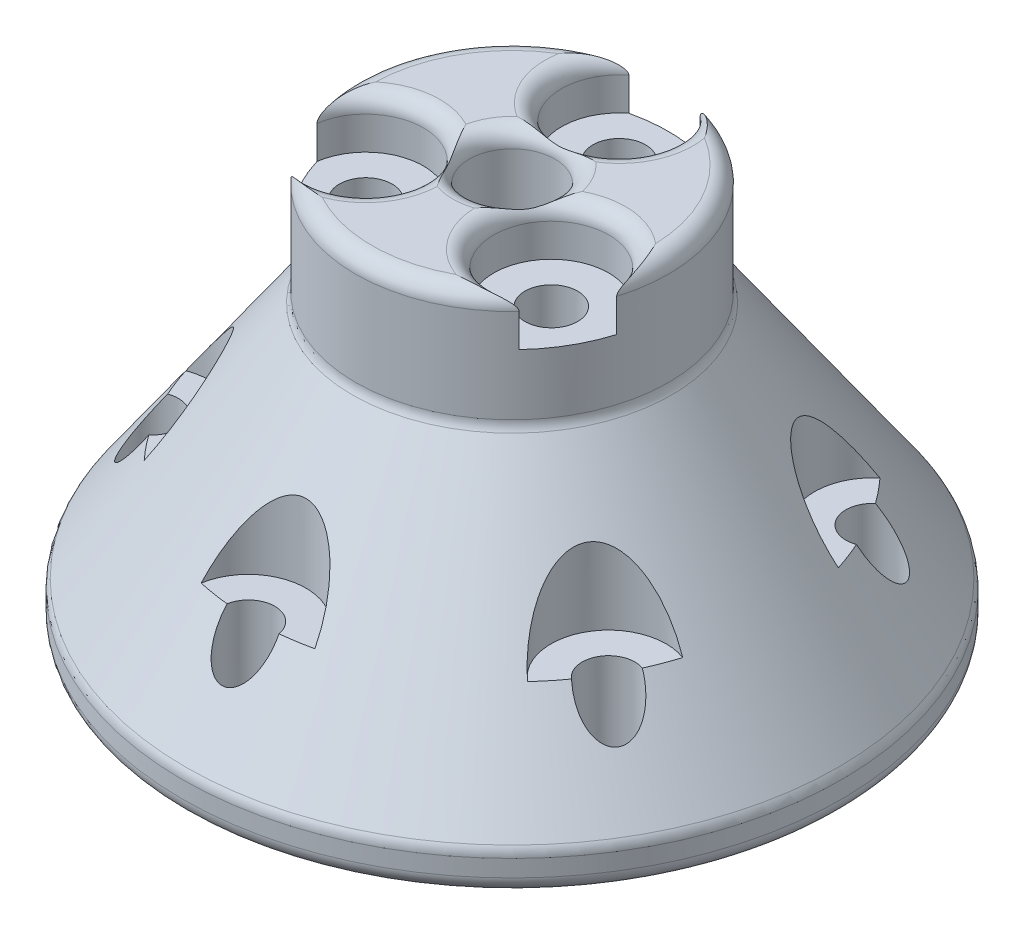
SolidWorks part; units mm, degrees
ref_plane "Front Plane" through (0, 0, 0) normal (0, 0, 1) x (1, 0, 0)
ref_plane "Top Plane" through (0, 0, 0) normal (0, 1, 0) x (1, 0, 0)
ref_plane "Right Plane" through (0, 0, 0) normal (1, 0, 0) x (0, 0, -1)
sketch "Sketch1" plane through (0, 0, 0) normal (0, 1, 0) x (1, 0, 0)
  circle A0 centre (0, 0) radius 20
  circle A1 centre (0, 0) radius 2.6
  dimension "D1" = 5.2
  dimension "D2" = 40
extrude "Boss-Extrude1" add sketch "Sketch1" along normal up to surface (24.34 mm away)
sketch "Sketch6" plane through (0, 24.34, 0) normal (0, 1, 0) x (1, 0, 0)
  circle A0 centre (0, 0) radius 9.5
  circle A1 centre (0, 0) radius 20 construction
  circle A2 centre (0, 0) radius 20
  dimension "D1" = 19
extrude "Cut-Extrude5" cut sketch "Sketch6" against normal blind 5
chamfer "Chamfer1" distance 17 angle 35 1 edges at (0, 19.34, 20) first distance on face at (0, 0, 20)
sketch "Sketch2" plane through (0, 0, 0) normal (0, -1, 0) x (1, 0, 0)
  line L0 (0, 0) -> (0, 16) construction
  circle A0 centre (0, 16) radius 1.6
  dimension "D1" = 3.2
  dimension "D2" = 16
extrude "Cut-Extrude1" cut sketch "Sketch2" against normal through all
sketch "Sketch5" plane through (0, 24.34, 0) normal (0, 1, 0) x (1, 0, 0)
  circle A4 centre (0, -16) radius 3.5
  circle A5 centre (0, -16) radius 1.6 construction
  circle A6 centre (0, -16) radius 1.6 construction
  dimension "D1" = 7
extrude "Cut-Extrude4" cut sketch "Sketch5" against normal blind 16
pattern_circular "CirPattern1" count 6 over 360 about axis through (0, 80.9085, 0) along (0, -1, 0) of "Cut-Extrude1", "Cut-Extrude4"
sketch "Sketch3" plane through (0, 24.34, 0) normal (0, 1, 0) x (1, 0, 0)
  line L0 (0, 0) -> (0, 6.5) construction
  circle A0 centre (0, 6.5) radius 1.6
  dimension "D1" = 3.2
  dimension "D2" = 6.5
extrude "Cut-Extrude2" cut sketch "Sketch3" against normal through all
sketch "Sketch4" plane through (0, 24.34, 0) normal (0, 1, 0) x (1, 0, 0)
  circle A0 centre (0, 6.5) radius 3.5
  dimension "D1" = 7
extrude "Cut-Extrude3" cut sketch "Sketch4" against normal blind 3
pattern_circular "CirPattern2" count 3 over 360 about axis through (0, 80.9085, 0) along (0, -1, 0) of "Cut-Extrude2", "Cut-Extrude3"
fillet "Fillet1" radius 1 10 edges at (0, 24.34, -2.6) (0, 24.34, -3) (-2.5981, 24.34, 1.5) (2.5981, 24.34, 1.5) (0, 0, 20) (-8.2272, 24.34, -4.75) (8.2272, 24.34, -4.75) (0, 24.34, 9.5) (0, 2.34, 20) (0, 17.3356, -9.5)
